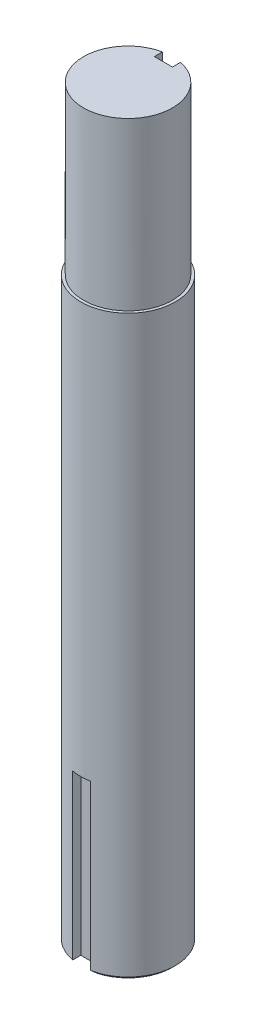
SolidWorks part; units mm, degrees
ref_plane "Front Plane" through (0, 0, 0) normal (0, 0, 1) x (1, 0, 0)
ref_plane "Top Plane" through (0, 0, 0) normal (0, 1, 0) x (1, 0, 0)
ref_plane "Right Plane" through (0, 0, 0) normal (1, 0, 0) x (0, 0, -1)
sketch "Sketch1" plane through (0, 0, 0) normal (0, 0, 1) x (1, 0, 0)
  line L5 (8.5, 134) -> (0, 134)
  line L6 (8.5, 134) -> (8.5, 0)
  line L7 (8.5, 0) -> (0, 0)
  line L8 (0, 134) -> (0, 0)
  line L9 (8.5, 134) -> (0, 0) construction
  line L10 (8.5, 0) -> (0, 134) construction
  point P0 (4.25, 67)
  dimension "D1" = 8.5
  dimension "D2" = 134
revolve "Revolve1" add sketch "Sketch1" angle 360 about L8
sketch "Sketch2" plane through (0, 0, 0) normal (0, -1, 0) x (1, 0, 0)
  line L1 (-1.625, 10.125) -> (1.625, 10.125)
  line L2 (-1.625, 10.125) -> (-1.625, 6.875)
  line L3 (-1.625, 6.875) -> (1.625, 6.875)
  line L4 (1.625, 10.125) -> (1.625, 6.875)
  line L5 (-1.625, 10.125) -> (1.625, 6.875) construction
  line L6 (-1.625, 6.875) -> (1.625, 10.125) construction
  circle A0 centre (0, 0) radius 8.5 construction
  point P0 (0, 8.5)
  dimension "D1" = 3.25
extrude "Cut-Extrude1" cut sketch "Sketch2" against normal blind 30
ref_axis "Axis1" through (0, 0, 0) along (0, 1, 0)
chamfer "Chamfer1" distance 0.5 angle 45 5 edges at (0, 134, 8.5) (-1.625, 0, 7.6091) (0, 0, 6.875) (1.625, 0, 7.6091) (0, 0, -8.5)
sketch "Sketch4" plane through (0, 134, 0) normal (0, 1, 0) x (1, 0, 0)
  circle A0 centre (0, 0) radius 8
  dimension "D1" = 16
extrude "Cut-Extrude3" cut sketch "Sketch4" against normal blind 30 flip side to cut
sketch "Sketch3" plane through (0, 134, 0) normal (0, 1, 0) x (1, 0, 0)
  line L1 (-1.625, 9.625) -> (1.625, 9.625)
  line L2 (-1.625, 9.625) -> (-1.625, 6.375)
  line L3 (-1.625, 6.375) -> (1.625, 6.375)
  line L4 (1.625, 9.625) -> (1.625, 6.375)
  line L5 (-1.625, 9.625) -> (1.625, 6.375) construction
  line L6 (-1.625, 6.375) -> (1.625, 9.625) construction
  circle A1 centre (0, 0) radius 8 construction
  point P0 (0, 8)
  point P7 (0, 0)
  point P9 (0, 0)
  dimension "D1" = 3.25
extrude "Cut-Extrude2" cut sketch "Sketch3" against normal blind 25
